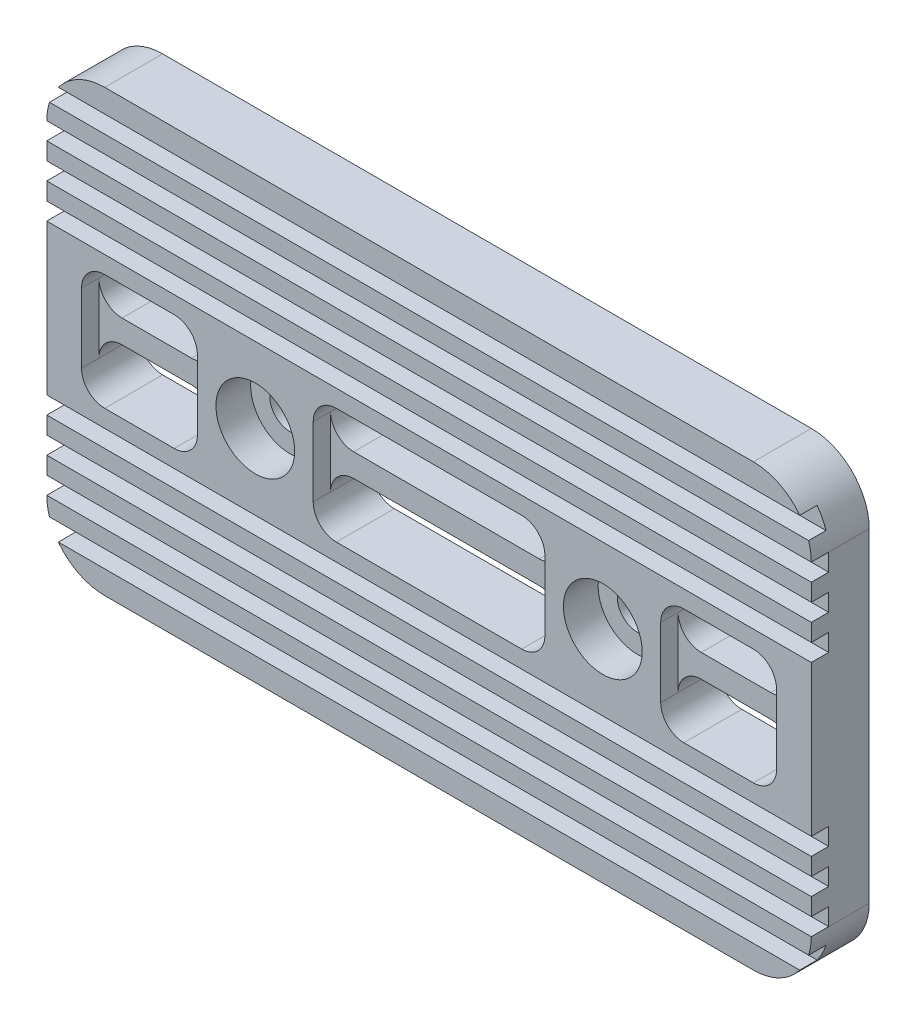
SolidWorks part; units mm, degrees
material "Vero PureWhite"
ref_plane "前视基准面" through (0, 0, 0) normal (0, 0, 1) x (1, 0, 0)
ref_plane "上视基准面" through (0, 0, 0) normal (0, 1, 0) x (1, 0, 0)
ref_plane "右视基准面" through (0, 0, 0) normal (1, 0, 0) x (0, 0, -1)
sketch "草图1" plane through (0, 0, 0) normal (0, 0, 1) x (1, 0, 0)
  line L0 (0, -55) -> (0, 55) construction
  line L1 (-33, 19) -> (33, 19)
  line L2 (-33, 19) -> (-33, -19)
  line L3 (-33, -19) -> (33, -19)
  line L4 (33, 19) -> (33, -19)
  line L5 (-33, 19) -> (33, -19) construction
  line L6 (-33, -19) -> (33, 19) construction
  circle A0 centre (-15, 0) radius 1.75
  circle A1 centre (15, 0) radius 1.75
  point P0 (0, 0)
  dimension "D4" = 3.5
  dimension "D1" = 66
  dimension "D2" = 38
  dimension "D3" = 15
extrude "凸台-拉伸1" add sketch "草图1" along normal blind 5
sketch "草图2" plane through (0, 0, 5) normal (0, 0, 1) x (1, 0, 0)
  circle A0 centre (-15, 0) radius 3.4
  circle A1 centre (15, 0) radius 3.4
  dimension "D1" = 6.8
extrude "切除-拉伸1" cut sketch "草图2" against normal blind 3
sketch "草图3" plane through (-33, 0, 0) normal (-1, 0, 0) x (0, 0, 1)
  line L0 (5, 19) -> (5, -19) construction
  line L1 (5, 17) -> (3.5, 17)
  line L2 (5, 17) -> (5, 15.5)
  line L3 (5, 15.5) -> (3.5, 15.5)
  line L4 (3.5, 17) -> (3.5, 15.5)
  line L5 (5, 19) -> (0, 19) construction
  line L6 (5, 14) -> (3.5, 14)
  line L7 (3.5, 14) -> (3.5, 12.5)
  line L8 (5, 14) -> (5, 12.5)
  line L9 (5, 12.5) -> (3.5, 12.5)
  line L10 (5, 11) -> (3.5, 11)
  line L11 (3.5, 11) -> (3.5, 9.5)
  line L12 (5, 11) -> (5, 9.5)
  line L13 (5, 9.5) -> (3.5, 9.5)
  line L14 (55, 0) -> (-55, 0) construction
  line L15 (5, -9.5) -> (3.5, -9.5)
  line L16 (5, -11) -> (5, -9.5)
  line L17 (3.5, -11) -> (3.5, -9.5)
  line L18 (5, -11) -> (3.5, -11)
  line L19 (5, -12.5) -> (3.5, -12.5)
  line L20 (5, -14) -> (5, -12.5)
  line L21 (3.5, -14) -> (3.5, -12.5)
  line L22 (5, -14) -> (3.5, -14)
  line L23 (3.5, -17) -> (3.5, -15.5)
  line L24 (5, -15.5) -> (3.5, -15.5)
  line L25 (5, -17) -> (5, -15.5)
  line L26 (5, -17) -> (3.5, -17)
  dimension "D1" = 1.5
  dimension "D2" = 1.5
  dimension "D3" = 2
  dimension "D5" = 1.5
  dimension "D4" = 3
extrude "切除-拉伸2" cut sketch "草图3" against normal blind 73
sketch "草图4" plane through (0, 0, 5) normal (0, 0, 1) x (1, 0, 0)
  line L0 (-33, 9.5) -> (-33, -9.5) construction
  line L1 (-33, 8) -> (-23, 8)
  line L2 (-33, 8) -> (-33, 6.5)
  line L3 (-33, 6.5) -> (-23, 6.5)
  line L4 (-23, 8) -> (-23, 6.5)
  line L5 (33, 9.5) -> (-33, 9.5) construction
  line L6 (-33, -6.5) -> (-23, -6.5)
  line L7 (-33, -6.5) -> (-33, -8)
  line L8 (-33, -8) -> (-23, -8)
  line L9 (-23, -6.5) -> (-23, -8)
  line L10 (33, -9.5) -> (-33, -9.5) construction
  line L11 (2.75, 0) -> (-2.75, 0) construction
  line L12 (-33, 5) -> (-23, 5) construction
  line L13 (-33, 5) -> (-33, -5) construction
  line L14 (-33, -5) -> (-23, -5) construction
  line L15 (-23, 5) -> (-23, -5) construction
  line L16 (-10, 8) -> (10, 8)
  line L17 (-10, 8) -> (-10, 6.5)
  line L18 (-10, 6.5) -> (10, 6.5)
  line L19 (10, 8) -> (10, 6.5)
  line L20 (-10, 5) -> (10, 5) construction
  line L21 (-10, 5) -> (-10, -5) construction
  line L22 (-10, -5) -> (10, -5) construction
  line L23 (10, 5) -> (10, -5) construction
  line L24 (10, -8) -> (10, -6.5)
  line L25 (-10, -6.5) -> (10, -6.5)
  line L26 (-10, -8) -> (-10, -6.5)
  line L27 (-10, -8) -> (10, -8)
  line L28 (0, -2.75) -> (0, 2.75) construction
  line L29 (23, 5) -> (23, -5) construction
  line L30 (33, -5) -> (23, -5) construction
  line L31 (33, 5) -> (33, -5) construction
  line L32 (33, 5) -> (23, 5) construction
  line L33 (23, -6.5) -> (23, -8)
  line L34 (33, -8) -> (23, -8)
  line L35 (33, -6.5) -> (33, -8)
  line L36 (33, -6.5) -> (23, -6.5)
  line L37 (23, 8) -> (23, 6.5)
  line L38 (33, 6.5) -> (23, 6.5)
  line L39 (33, 8) -> (33, 6.5)
  line L40 (33, 8) -> (23, 8)
  point P26 (0, 8)
  point P28 (0, 5)
  dimension "D1" = 1.5
  dimension "D2" = 1.5
  dimension "D3" = 1.5
  dimension "D4" = 1.5
  dimension "D5" = 10
  dimension "D6" = 10
  dimension "D7" = 1.5
  dimension "D8" = 1.5
  dimension "D9" = 20
  dimension "D10" = 1.5
extrude "切除-拉伸3" cut sketch "草图4" against normal blind 1.5
fillet "圆角1" radius 5 4 edges at (33, -19, 2.5) (-33, -19, 2.5) (33, 19, 2.5) (-33, 19, 2.5)
sketch "草图5" plane through (0, 0, 5) normal (0, 0, 1) x (1, 0, 0)
  line L1 (-23, 8) -> (-10, 8)
  line L2 (-23, 8) -> (-23, 6.5)
  line L3 (-23, 6.5) -> (-10, 6.5)
  line L4 (-10, 8) -> (-10, 6.5)
  line L5 (10, 8) -> (23, 8)
  line L6 (10, 8) -> (10, 6.5)
  line L7 (10, 6.5) -> (23, 6.5)
  line L8 (23, 8) -> (23, 6.5)
  line L9 (-23, -6.5) -> (-10, -6.5)
  line L10 (-23, -6.5) -> (-23, -8)
  line L11 (-23, -8) -> (-10, -8)
  line L12 (-10, -6.5) -> (-10, -8)
  line L13 (10, -6.5) -> (23, -6.5)
  line L14 (10, -6.5) -> (10, -8)
  line L15 (10, -8) -> (23, -8)
  line L16 (23, -6.5) -> (23, -8)
extrude "切除-拉伸4" cut sketch "草图5" against normal blind 1.5
sketch "草图6" plane through (0, 0, 5) normal (0, 0, 1) x (1, 0, 0)
  line L0 (-33, 6.5) -> (33, 6.5) construction
  line L1 (-10, 5) -> (10, 5)
  line L2 (-10, 5) -> (-10, -5)
  line L3 (-10, -5) -> (10, -5)
  line L4 (10, 5) -> (10, -5)
  line L5 (33, -6.5) -> (-33, -6.5) construction
  line L6 (33, -6.5) -> (33, 6.5) construction
  line L7 (20, 5) -> (30, 5)
  line L8 (20, 5) -> (20, -5)
  line L9 (20, -5) -> (30, -5)
  line L10 (30, 5) -> (30, -5)
  line L11 (0, -2.75) -> (0, 2.75) construction
  line L12 (-30, 5) -> (-30, -5)
  line L13 (-20, -5) -> (-30, -5)
  line L14 (-20, 5) -> (-20, -5)
  line L15 (-20, 5) -> (-30, 5)
  dimension "D1" = 1.5
  dimension "D2" = 1.5
  dimension "D3" = 10
  dimension "D4" = 10
  dimension "D5" = 3
  dimension "D6" = 10
extrude "切除-拉伸5" cut sketch "草图6" against normal blind 11.5
fillet "圆角2" radius 2 12 edges at (-30, 5, 2.5) (-30, -5, 2.5) (-20, -5, 2.5) (-20, 5, 2.5) (30, -5, 2.5) (20, -5, 2.5) (20, 5, 2.5) (30, 5, 2.5) (-10, -5, 2.5) (10, -5, 2.5) (10, 5, 2.5) (-10, 5, 2.5)
sketch "草图7" plane through (0, 0, 5) normal (0, 0, 1) x (1, 0, 0)
  line L0 (-30, 3) -> (-30, -3) construction
  line L1 (-30, 1) -> (-20, 1)
  line L2 (-30, 1) -> (-30, -1)
  line L3 (-30, -1) -> (-20, -1)
  line L4 (-20, 1) -> (-20, -1)
  line L5 (-20, -3) -> (-20, 3) construction
  line L6 (-10, 3) -> (-10, -3) construction
  line L7 (-10, 1) -> (10, 1)
  line L8 (-10, 1) -> (-10, -1)
  line L9 (-10, -1) -> (10, -1)
  line L10 (10, 1) -> (10, -1)
  line L11 (10, -3) -> (10, 3) construction
  line L12 (20, 3) -> (20, -3) construction
  line L13 (20, 1) -> (30, 1)
  line L14 (20, 1) -> (20, -1)
  line L15 (20, -1) -> (30, -1)
  line L16 (30, 1) -> (30, -1)
  line L17 (30, -3) -> (30, 3) construction
  line L18 (-22, 5) -> (-28, 5) construction
  line L19 (-28, -5) -> (-22, -5) construction
  dimension "D1" = 4
  dimension "D2" = 4
extrude "凸台-拉伸2" add sketch "草图7" against normal up to surface (5 mm away) up to face at (-25, 0, 0)
sketch "草图8" plane through (0, 0, 5) normal (0, 0, 1) x (1, 0, 0)
  line L1 (-30, 1) -> (-20, 1)
  line L2 (-30, 1) -> (-30, -1)
  line L3 (-30, -1) -> (-20, -1)
  line L4 (-20, 1) -> (-20, -1)
  line L5 (-10, 1) -> (10, 1)
  line L6 (-10, 1) -> (-10, -1)
  line L7 (-10, -1) -> (10, -1)
  line L8 (10, 1) -> (10, -1)
  line L9 (20, 1) -> (30, 1)
  line L10 (20, 1) -> (20, -1)
  line L11 (20, -1) -> (30, -1)
  line L12 (30, 1) -> (30, -1)
extrude "切除-拉伸6" cut sketch "草图8" against normal blind 1.5
fillet "圆角3" radius 2 12 edges at (30, -1, 1.75) (30, 1, 1.75) (20, -1, 1.75) (20, 1, 1.75) (10, -1, 1.75) (10, 1, 1.75) (-10, -1, 1.75) (-10, 1, 1.75) (-30, -1, 1.75) (-20, -1, 1.75) (-20, 1, 1.75) (-30, 1, 1.75)
scale "缩放比例1" scale about origin uniform scaling yes scale factor 0.6
